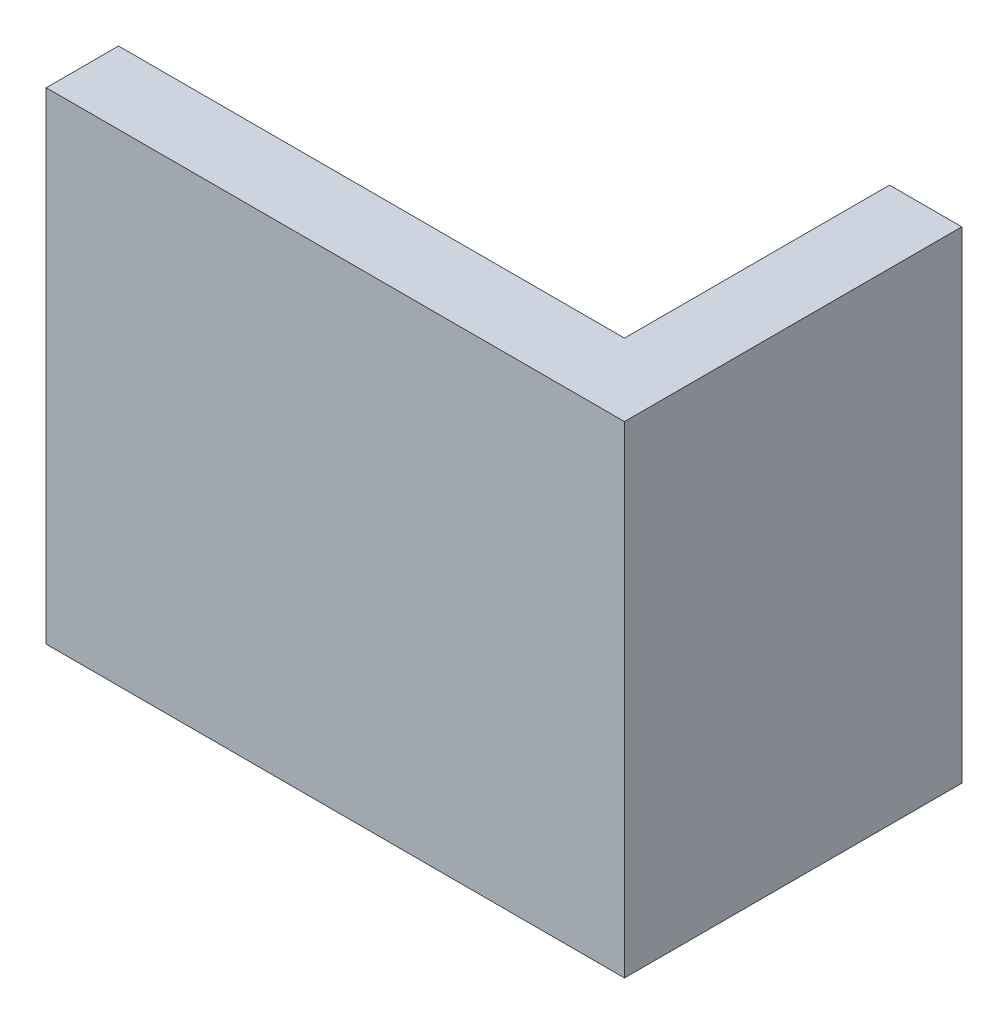
SolidWorks part; units mm, degrees
ref_plane "Front Plane" through (0, 0, 0) normal (0, 0, 1) x (1, 0, 0)
ref_plane "Top Plane" through (0, 0, 0) normal (0, 1, 0) x (1, 0, 0)
ref_plane "Right Plane" through (0, 0, 0) normal (1, 0, 0) x (0, 0, -1)
ref_axis "Axis1" through (-88.99, 0, 0) along (1, 0, 0)
sketch "Sketch1" plane through (0, 0, 0) normal (0, 1, 0) x (1, 0, 0)
  line L0 (9, -3) -> (9, 8)
  line L1 (-12, -6) -> (12, -6)
  line L2 (-12, -6) -> (-12, -3)
  line L3 (-12, -3) -> (9, -3)
  line L4 (12, -6) -> (12, 8)
  line L5 (9, 8) -> (12, 8)
  line L6 (0, -6) -> (0, 0) construction
  line L7 (-88.99, 0) -> (88.99, 0) construction
  point P8 (7, 8.5694)
  dimension "D1" = 3
  dimension "D2" = 3
  dimension "D3" = 21
  dimension "D4" = 3
  dimension "D5" = 8
extrude "Boss-Extrude1" add sketch "Sketch1" along normal mid plane 20
